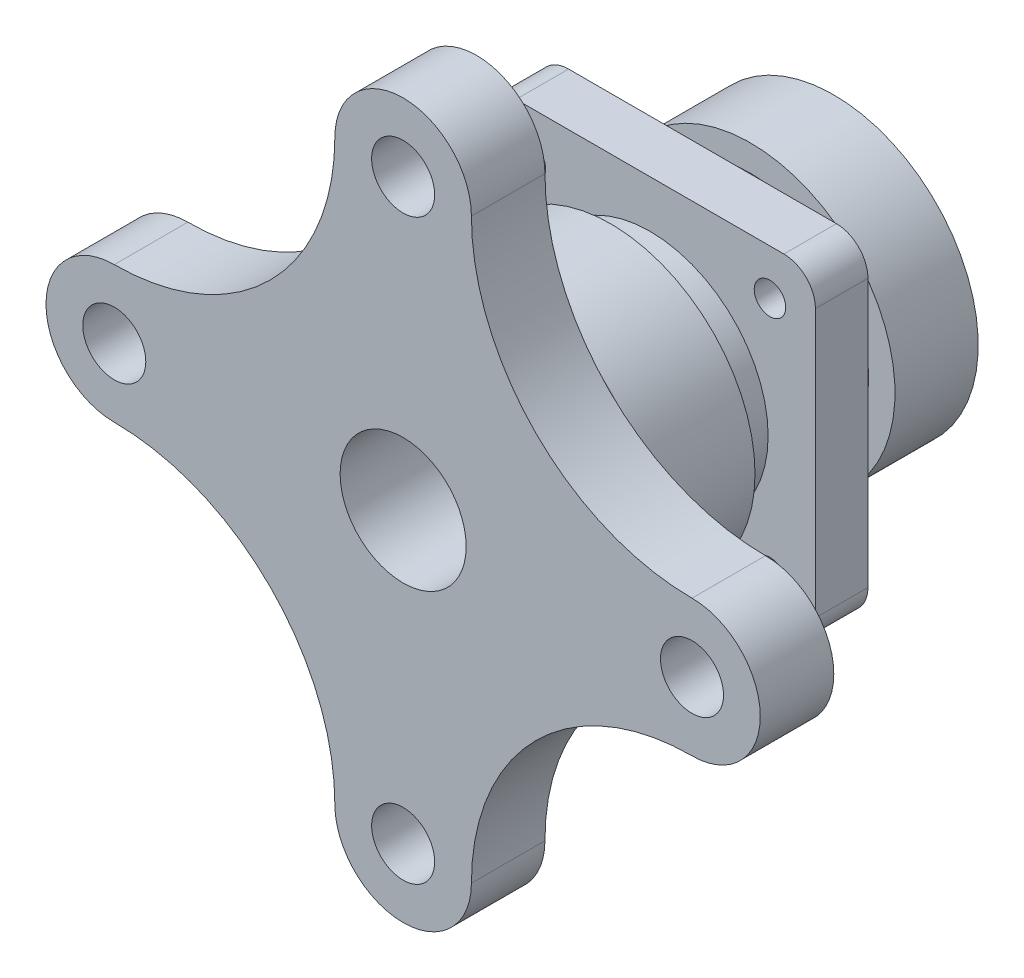
SolidWorks part; units mm, degrees
ref_plane "Front Plane" through (0, 0, 0) normal (0, 0, 1) x (1, 0, 0)
ref_plane "Top Plane" through (0, 0, 0) normal (0, 1, 0) x (1, 0, 0)
ref_plane "Right Plane" through (0, 0, 0) normal (1, 0, 0) x (0, 0, -1)
sketch "Sketch1" plane through (0, 0, 0) normal (0, 0, 1) x (1, 0, 0)
  circle A0 centre (0, 0) radius 20
  circle A1 centre (0, 0) radius 27.5
  dimension "D1" = 40
  dimension "D2" = 55
extrude "Boss-Extrude1" add sketch "Sketch1" along normal blind 88
ref_plane "Plane1" through (0, 0, 45) normal (0, 0, -1) x (-1, 0, 0)
sketch "Sketch2" plane through (0, 0, 45) normal (0, 0, -1) x (-1, 0, 0)
  line L0 (0, 0) -> (46.4229, 0) construction
  line L1 (-25.5, -31.5) -> (25.5, -31.5)
  line L2 (-31.5, -25.5) -> (-31.5, 25.5)
  line L3 (-25.5, 31.5) -> (25.5, 31.5)
  line L4 (31.5, -25.5) -> (31.5, 25.5)
  line L5 (-31.5, -31.5) -> (31.5, 31.5) construction
  line L6 (-31.5, 31.5) -> (31.5, -31.5) construction
  circle A0 centre (22.8466, 22.8466) radius 3
  circle A1 centre (-22.8466, -22.8466) radius 3
  circle A2 centre (22.8466, -22.8466) radius 3
  circle A3 centre (-22.8466, 22.8466) radius 3
  arc A4 (25.5, -31.5) -> (31.5, -25.5) centre (25.5, -25.5) ccw
  arc A5 (-25.5, -31.5) -> (-31.5, -25.5) centre (-25.5, -25.5) cw
  arc A6 (-31.5, 25.5) -> (-25.5, 31.5) centre (-25.5, 25.5) cw
  arc A7 (25.5, 31.5) -> (31.5, 25.5) centre (25.5, 25.5) cw
  circle A8 centre (0, 0) radius 27.5
  point P0 (0, 0)
  dimension "D3" = 6
  dimension "D4" = 6
  dimension "D1" = 63
  dimension "D2" = 63
  dimension "D5" = 32.31
extrude "Boss-Extrude2" add sketch "Sketch2" against normal blind 10
sketch "Sketch3" plane through (0, 0, 88) normal (0, 0, 1) x (1, 0, 0)
  line L0 (0, 42) -> (0, 55) construction
  line L1 (0, 0) -> (55, 0) construction
  line L2 (0, 55) -> (21.233, 55) construction
  line L3 (55, 0) -> (55, 23.4869) construction
  line L4 (13, 55) -> (13, 33.7853) construction
  line L5 (55, 13) -> (81.8117, 13) construction
  circle A0 centre (0, 0) radius 55 construction
  circle A1 centre (0, 55) radius 6
  circle A2 centre (55, 0) radius 6
  circle A3 centre (0, -55) radius 6
  circle A4 centre (-55, 0) radius 6
  arc A5 (12.9089, 53.4636) -> (-12.9089, 53.4636) centre (0, 55) ccw
  arc A6 (53.4636, -12.9089) -> (53.4636, 12.9089) centre (55, 0) ccw
  arc A7 (-12.9089, -53.4636) -> (12.9089, -53.4636) centre (0, -55) ccw
  arc A8 (-53.4636, 12.9089) -> (-53.4636, -12.9089) centre (-55, 0) ccw
  arc A9 (13, 55) -> (55, 13) centre (55, 55) ccw
  arc A10 (55, -13) -> (13, -55) centre (55, -55) ccw
  arc A11 (-13, -55) -> (-55, -13) centre (-55, -55) ccw
  arc A12 (-55, 13) -> (-13, 55) centre (-55, 55) ccw
  circle A13 centre (0, 0) radius 12
  point P10 (13, 55)
  point P15 (0, 0)
  point P16 (55, 13)
  point P23 (0, 0)
  point P41 (0, 0)
  circle M1 centre (0, 0) radius 27.5
  circle M2 centre (0, 0) radius 20
  dimension "D1" = 110
  dimension "D2" = 4
  dimension "D3" = 12
  dimension "D5" = 26
  dimension "D7" = 24
  dimension "D6" = 4
  dimension "D4" = 4
extrude "Boss-Extrude3" add sketch "Sketch3" along normal blind 14 contours A12 A8 A11 A7 A10 A6 A9 A5 A4 A3 A2 A1 M1 | M1 M2 | A13 M2 region at (23.9415, 23.9415, 88) region at (-26.7222, 0, 88) region at (-19.4343, 0, 88)
sketch "Sketch4" plane through (0, 0, 45) normal (0, 0, -1) x (-1, 0, 0)
  circle A0 centre (22.8466, 22.8466) radius 9
  circle A1 centre (22.8466, -22.8466) radius 9
  circle A2 centre (-22.8466, -22.8466) radius 9
  circle A3 centre (-22.8466, 22.8466) radius 9
  point P12 (0, 0)
  dimension "D2" = 18
  dimension "D1" = 4
sketch "Sketch5" plane through (0, 0, 55) normal (0, 0, 1) x (1, 0, 0)
  circle A0 centre (22.8466, 22.8466) radius 9
  circle A1 centre (22.8466, -22.8466) radius 9
  circle A2 centre (-22.8466, -22.8466) radius 9
  circle A3 centre (-22.8466, 22.8466) radius 9
  point P12 (0, 0)
  dimension "D1" = 18
  dimension "D2" = 4
fillet "Fillet3" radius 6 1 edges at (27.5, 0, 88)
ref_plane "Plane2" through (0, 0, 45) normal (0, 0, -1) x (-1, 0, 0)
sketch "Sketch6" plane through (0, 0, 45) normal (0, 0, -1) x (-1, 0, 0)
  circle A0 centre (0, 0) radius 20
  circle A1 centre (0, 0) radius 12
  dimension "D1" = 24
extrude "Boss-Extrude4" add sketch "Sketch6" against normal up to surface and the other way blind 7.5 up to face at (33.5, 0, 88)
sketch "Sketch7" plane through (0, 0, 0) normal (0, 0, -1) x (-1, 0, 0)
  circle A0 centre (0, 0) radius 27.5
extrude "Cut-Extrude1" cut sketch "Sketch7" against normal blind 20
sketch "Sketch8" plane through (0, 0, 20) normal (0, 0, -1) x (-1, 0, 0)
  circle A0 centre (0, 0) radius 22.5
  dimension "D1" = 45
extrude "Cut-Extrude2" cut sketch "Sketch8" against normal up to surface (17.5 mm away) up to face at (-20, 0, 37.5)
ref_plane "Plane4" through (0, 0, 37.75) normal (0, 0, -1) x (-1, 0, 0)
sketch "Sketch11" plane through (0, 0, 37.75) normal (0, 0, -1) x (-1, 0, 0)
  circle A0 centre (0, 0) radius 27.5
  circle A1 centre (0, 0) radius 22.5
extrude "Cut-Extrude5" cut sketch "Sketch11" against normal up to surface and the other way blind 1.9 up to face at (-27.5, 0, 45)
sketch "Sketch12" plane through (0, 0, 20) normal (0, 0, -1) x (-1, 0, 0)
  circle A0 centre (0, 0) radius 22.5
  circle A1 centre (0, 0) radius 27.5
  dimension "D1" = 5
extrude "Boss-Extrude5" add sketch "Sketch12" against normal up to surface (15.85 mm away) up to face at (-27.5, 0, 35.85)
sketch "Sketch13" plane through (0, 0, 37.5) normal (0, 0, -1) x (-1, 0, 0)
  circle A0 centre (0, 0) radius 12
  circle A1 centre (0, 0) radius 22.5
extrude "Boss-Extrude6" add sketch "Sketch13" along normal blind 5.65
ref_plane "Plane6" through (0, 0, 55) normal (0, 0, 1) x (1, 0, 0)
sketch "Sketch15" plane through (0, 0, 55) normal (0, 0, 1) x (1, 0, 0)
  circle A0 centre (0, 0) radius 22.5
  circle A1 centre (0, 0) radius 27.5
extrude "Cut-Extrude7" cut sketch "Sketch15" along normal blind 7.5
